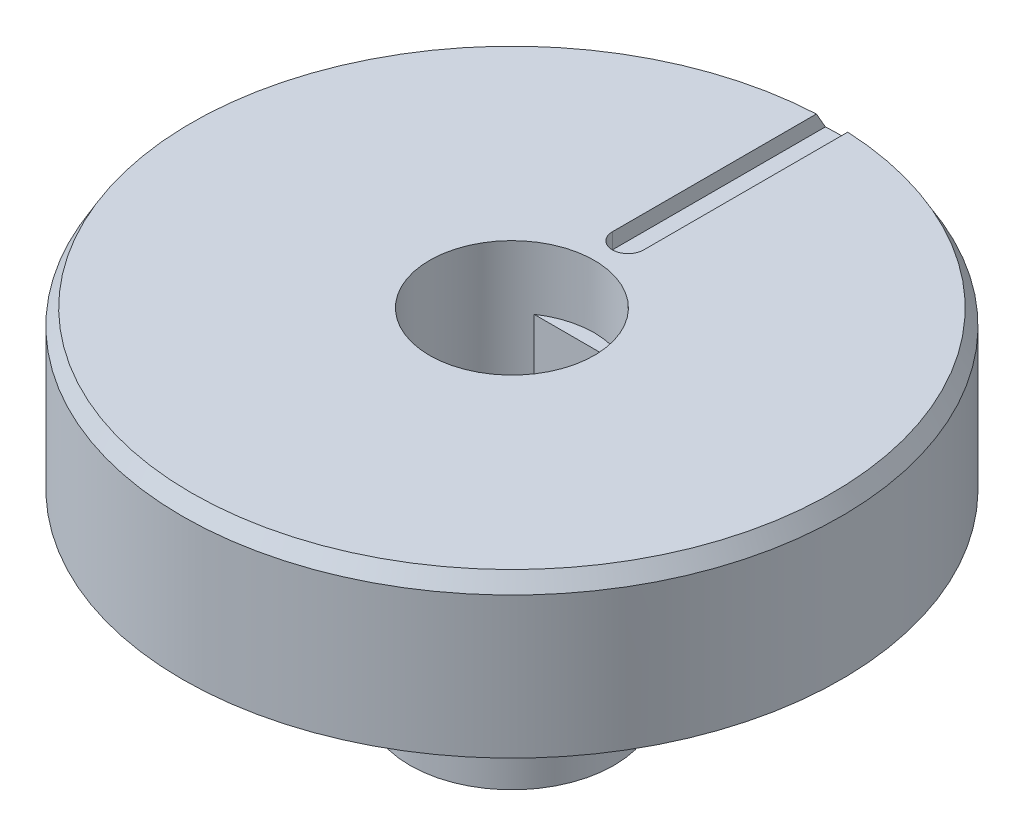
SolidWorks part; units mm, degrees
ref_plane "Front Plane" through (0, 0, 0) normal (0, 0, 1) x (1, 0, 0)
ref_plane "Top Plane" through (0, 0, 0) normal (0, 1, 0) x (1, 0, 0)
ref_plane "Right Plane" through (0, 0, 0) normal (1, 0, 0) x (0, 0, -1)
sketch "Sketch1" plane through (0, 0, 0) normal (0, 1, 0) x (1, 0, 0)
  circle A0 centre (0, 0) radius 8.6
  circle A1 centre (0, 0) radius 10.5
  dimension "D1" = 17.2
  dimension "D2" = 21
extrude "Boss-Extrude1" add sketch "Sketch1" against normal blind 4
ref_plane "Plane1" through (0, 0, 8.6) normal (0, 0, -1) x (-1, 0, 0)
sketch "Sketch2" plane through (0, 0, 8.6) normal (0, 0, -1) x (-1, 0, 0)
  line L0 (0.4, -3.75) -> (-0.4, -3.75)
  line L1 (0.4, -3.75) -> (0.4, -1.9)
  line L2 (0.4, -1.9) -> (2.3, 0)
  line L3 (10.5, 0) -> (-10.5, 0) construction
  line L4 (2.3, 0) -> (-2.3, 0)
  line L5 (-2.3, 0) -> (-0.4, -1.9)
  line L6 (-0.4, -1.9) -> (-0.4, -3.75)
  point P2 (0, -3.75)
  dimension "D1" = 3.75
  dimension "D2" = 135
  dimension "D3" = 135
  dimension "D4" = 0.8
  dimension "D5" = 1.9
extrude "Boss-Extrude2" add sketch "Sketch2" along normal blind 1.25
ref_plane "Plane2" through (0, 0, -8.6) normal (0, 0, 1) x (1, 0, 0)
extrude "Boss-Extrude3" add sketch "Sketch2<2>" against normal blind 1.25 from surface starting at plane "Plane2"
sketch "Sketch2<2>" plane through (0, 0, 8.6) normal (0, 0, -1) x (-1, 0, 0) same geometry as "Sketch2"
sketch "Sketch3" plane through (0, 0, 0) normal (0, 1, 0) x (1, 0, 0)
  circle A1 centre (0, 0) radius 10.5
  circle A2 centre (0, 0) radius 10.5
  dimension "D1" = 0
extrude "Boss-Extrude4" add sketch "Sketch3" along normal blind 1
sketch "Sketch5" plane through (0, 0, 0) normal (0, -1, 0) x (1, 0, 0)
  circle A1 centre (0, 0) radius 3.25
  dimension "D2" = 6.5
extrude "Boss-Extrude5" add sketch "Sketch5" along normal blind 10
fillet "Fillet2" radius 0.75 1 edges at (0, 0, 3.25)
sketch "Sketch4" plane through (0, 1, 0) normal (0, 1, 0) x (1, 0, 0)
  line L0 (-1.4697, 2.175) -> (1.4697, 2.175)
  line L1 (-3.1755, -2.625) -> (3.3726, -2.625) construction
  arc A0 (-1.4697, 2.175) -> (1.4697, 2.175) centre (0, 0) ccw
  dimension "D1" = 5.25
  dimension "D2" = 4.8
extrude "Cut-Extrude1" cut sketch "Sketch4" against normal blind 5.25
fillet "Fillet1" radius 0.25 4 edges at (-0.4, -3.75, 7.9703) (0.4, -3.75, 7.9703) (-0.4, -3.75, -7.9703) (0.4, -3.75, -7.9703)
sketch "Sketch7" plane through (0, 1, 0) normal (0, 1, 0) x (1, 0, 0)
  circle A2 centre (0, 0) radius 2.625
  arc A3 (-1.4697, 2.175) -> (1.4697, 2.175) centre (0, 0) ccw construction
extrude "Cut-Extrude2" cut sketch "Sketch7" against normal blind 2
sketch "Sketch9" plane through (0, 1, 0) normal (0, 1, 0) x (1, 0, 0)
  line L0 (0, 3.7) -> (0, 13.7) construction
  line L1 (-0.5, 3.7) -> (-0.5, 13.7)
  line L2 (0.5, 3.7) -> (0.5, 13.7)
  arc A0 (-0.5, 3.7) -> (0.5, 3.7) centre (0, 3.7) ccw
  arc A1 (0.5, 13.7) -> (-0.5, 13.7) centre (0, 13.7) ccw
  point P3 (0, 8.7)
  dimension "D1" = 1
  dimension "D2" = 10
  dimension "D3" = 3.7
extrude "Cut-Extrude3" cut sketch "Sketch9" against normal blind 0.5
sketch "Sketch10" plane through (0, -10, 0) normal (0, -1, 0) x (1, 0, 0)
  line L1 (1.8042, 0) -> (0.9021, 1.5625)
  line L2 (0.9021, 1.5625) -> (-0.9021, 1.5625)
  line L3 (-0.9021, 1.5625) -> (-1.8042, 0)
  line L4 (-1.8042, 0) -> (-0.9021, -1.5625)
  line L5 (-0.9021, -1.5625) -> (0.9021, -1.5625)
  line L6 (0.9021, -1.5625) -> (1.8042, 0)
  circle A0 centre (0, 0) radius 1.5625 construction
  dimension "D1" = 3.125
extrude "Cut-Extrude4" cut sketch "Sketch10" against normal blind 4
chamfer "Chamfer2" distance 0.25 angle 45 6 edges at (1.3532, -10, 0.7813) (1.3532, -10, -0.7813) (0, -10, -1.5625) (-1.3532, -10, -0.7813) (-1.3532, -10, 0.7813) (0, -10, 1.5625)
chamfer "Chamfer3" distance 0.5 angle 30 1 edges at (0, 1, 10.5) first distance on face at (0, 0.75, -5.244)
